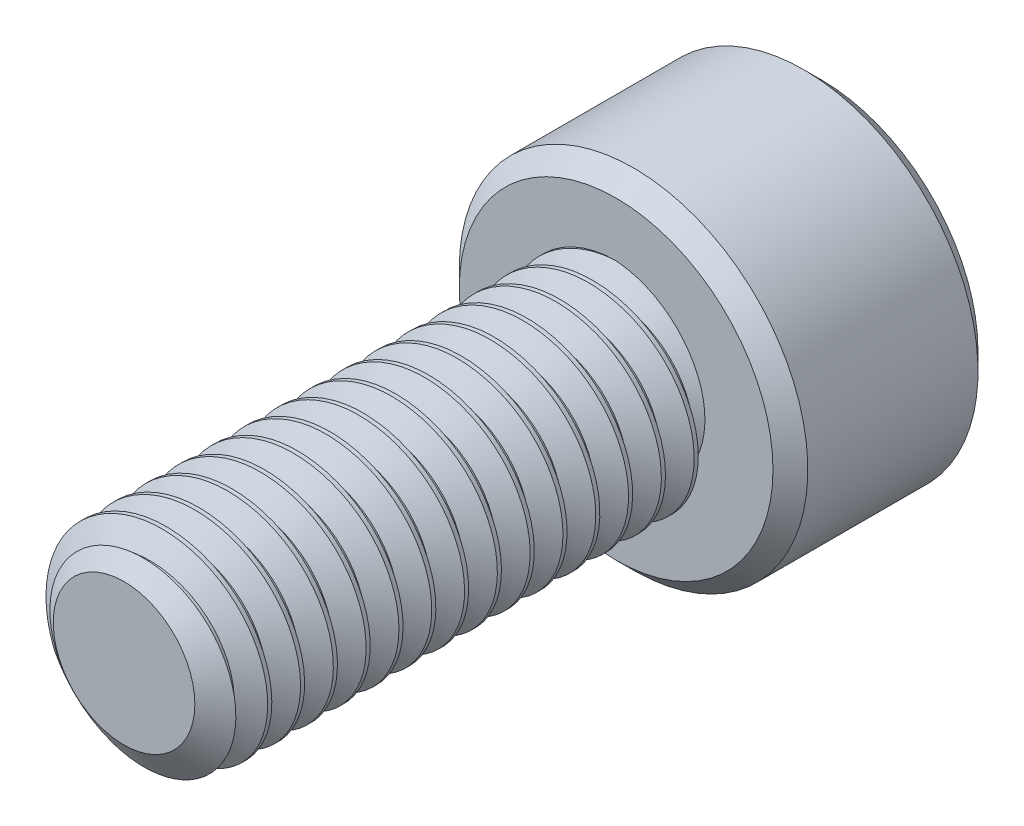
SolidWorks part; units mm, degrees
ref_plane "Front Plane" through (0, 0, 0) normal (0, 0, 1) x (1, 0, 0)
ref_plane "Top Plane" through (0, 0, 0) normal (0, 1, 0) x (1, 0, 0)
ref_plane "Right Plane" through (0, 0, 0) normal (1, 0, 0) x (0, 0, -1)
sketch "Sketch1" plane through (0, 0, 0) normal (0, 0, 1) x (1, 0, 0)
  circle A0 centre (0, 0) radius 2.5
  dimension "OD" = 5
extrude "Extrude1" add sketch "Sketch1" against normal blind 12
sketch "Sketch2" plane through (0, 0, 0) normal (0, 0, 1) x (1, 0, 0)
  circle A0 centre (0, 0) radius 2.5 construction
  circle A1 centre (0, 0) radius 2.5
curve "Helix/Spiral1" pitch 0.8 height 12.8 turns 16 parameters "pitch"=0.8
sketch "Sketch3" plane through (0, 0, 0) normal (1, 0, 0) x (0, 0, -1)
  line L0 (-0.7, 2.5) -> (-0.4, 1.9804)
  line L1 (-0.4, 1.9804) -> (-0.3, 1.9804)
  line L2 (-0.3, 1.9804) -> (0, 2.5)
  line L3 (-0.7, 2.5) -> (0, 2.5)
  line L4 (-0.35, 2.5) -> (-0.35, 1.9804) construction
  line L5 (-0.55, 2.2402) -> (-0.15, 2.2402) construction
  line L6 (0, 2.5) -> (0, -2.5) construction
  dimension "D1" = 0.1
  dimension "D2" = 0.4
  dimension "D3" = 60
sweep "Cut-Sweep1" cut profiles "Sketch3" path "Helix/Spiral1"
sketch "Sketch4" plane through (0, 0, 0) normal (1, 0, 0) x (0, 0, -1)
  line L0 (0.5417, 2.5) -> (0, 1.7264)
  line L1 (0, 1.7264) -> (0, 2.5)
  line L2 (0.5417, 2.5) -> (0, 2.5)
  line L3 (-0.7, 2.5) -> (0, 2.5) construction
  line L4 (0, 0) -> (7.0209, 0) construction
  dimension "D1" = 55
  dimension "D2" = 0.254
revolve "Cut-Revolve1" cut sketch "Sketch4" angle 360 about L4
sketch "Sketch6" plane through (0, 0, -12) normal (0, 0, -1) x (-1, 0, 0)
  circle A0 centre (0, 0) radius 4.25
  dimension "head dia" = 8.5
extrude "Extrude2" add sketch "Sketch6" along normal blind 5
sketch "Sketch7" plane through (0, 0, -17) normal (0, 0, -1) x (-1, 0, 0)
  line L1 (0, 2.3094) -> (-2, 1.1547)
  line L2 (-2, 1.1547) -> (-2, -1.1547)
  line L3 (-2, -1.1547) -> (0, -2.3094)
  line L4 (0, -2.3094) -> (2, -1.1547)
  line L5 (2, -1.1547) -> (2, 1.1547)
  line L6 (2, 1.1547) -> (0, 2.3094)
  circle A0 centre (0, 0) radius 2 construction
  dimension "hex dia" = 4
extrude "Cut-Extrude1" cut sketch "Sketch7" against normal blind 3
sketch "Sketch8" plane through (0, 0, -17) normal (0, 0, -1) x (-1, 0, 0)
  circle A0 centre (0, 0) radius 2.3094
extrude "Cut-Extrude2" cut sketch "Sketch8" against normal through all draft 45
chamfer "Chamfer1" distance 0.425 angle 45 2 edges at (-4.25, 0, -17) (-4.25, 0, -12)
sketch "Sketch10" plane through (0, 0, -12) normal (0, 0, 1) x (1, 0, 0)
  circle A1 centre (0, 0) radius 2.5
  circle A2 centre (0, 0) radius 2.5
  dimension "D1" = 0
ref_plane "Plane1" through (0, 0, 0) normal (0, 0, 1) x (1, 0, 0)
extrude "partial thread" [suppressed] add sketch "Sketch10" along normal up to surface (36 mm away) separate body
chamfer "Chamfer2" [suppressed] distance 0.1 angle 45
combine bodies "Combine1" [suppressed] operation type add bodies to combine 107 108
sketch "Sketch9" plane through (0, 0, 0) normal (1, 0, 0) x (0, 0, -1)
  line L0 (0, 2.5) -> (0, -2.5) construction
  line L1 (2, 2.5) -> (2, -2.5) construction
  dimension "D1" = 2
equation "\"D3@Helix/Spiral1\" = \"screw length@Extrude1\"+\"pitch@Helix/Spiral1\""
equation "\"D1@Sketch3\" = \"pitch@Helix/Spiral1\"*.125"
equation "\"D2@Sketch3\" = \"pitch@Helix/Spiral1\"*.5"
equation "\"D1@Cut-Extrude1\" = \"hex dia@Sketch7\"*.75"
equation "\"D1@Chamfer1\" = \"head dia@Sketch6\"*.05"
equation "\"D1@Sketch9\" = \"pitch@Helix/Spiral1\"*2.5"
equation "\"D1@Chamfer2\"=\"OD@Sketch1\"*.02"
